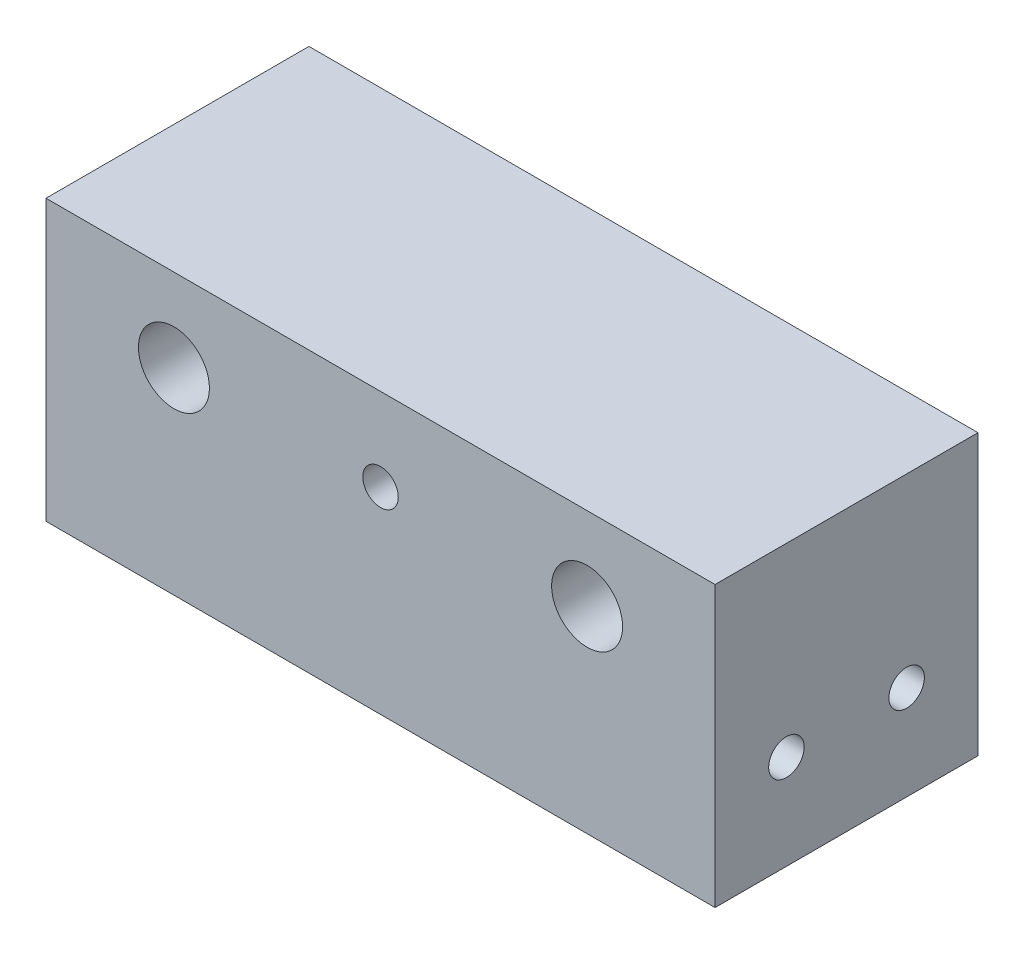
SolidWorks part; units mm, degrees
material "ABS"
ref_plane "X-Y Datum" through (0, 0, 0) normal (0, 0, 1) x (1, 0, 0)
ref_plane "X-Z Datum" through (0, 0, 0) normal (0, 1, 0) x (1, 0, 0)
ref_plane "Y-Z Datum" through (0, 0, 0) normal (1, 0, 0) x (0, 0, -1)
sketch "Sketch1" plane through (0, 0, 0) normal (0, 0, 1) x (1, 0, 0)
  line L1 (-28.275, 11.1125) -> (28.275, 11.1125)
  line L2 (-28.275, 11.1125) -> (-28.275, -11.1125)
  line L3 (-28.275, -11.1125) -> (28.275, -11.1125)
  line L4 (28.275, 11.1125) -> (28.275, -11.1125)
  line L5 (-28.275, 11.1125) -> (28.275, -11.1125) construction
  line L6 (-28.275, -11.1125) -> (28.275, 11.1125) construction
  point P0 (0, 0)
  dimension "D1" = 56.55
  dimension "D2" = 22.225
extrude "Boss-Extrude1" add sketch "Sketch1" along normal blind 22.225 contours L2 L3 L4 L1
sketch "Sketch2" plane through (0, 0, 22.225) normal (0, 0, 1) x (1, 0, 0)
  line L0 (-23.5453, 4.1125) -> (31.0951, 4.1125) construction
  line L1 (0, 11.1125) -> (0, -11.1125) construction
  line L2 (-28.275, 11.1125) -> (28.275, 11.1125) construction
  line L3 (-17.4625, 4.1125) -> (17.4625, 4.1125) construction
  line L4 (-28.275, -11.1125) -> (28.275, -11.1125) construction
  circle A0 centre (17.4625, 4.1125) radius 3
  circle A1 centre (-17.4625, 4.1125) radius 3
  circle A2 centre (0, 4.1125) radius 1.5
  point P10 (0, 4.1125)
  dimension "D1" = 6
  dimension "D4" = 3
  dimension "D2" = 34.925
  dimension "D3" = 7
extrude "Cut-Extrude1" cut sketch "Sketch2" against normal blind 10 contours A1 L0 L3 | L0 A1 L3 | L0 L3 A0 | L3 L0 A0 | A2 region at (17.4625, 4.1125, 22.225) region at (-17.4625, 4.1125, 22.225) region at (0, 4.1125, 22.225)
sketch "Sketch3" plane through (-28.275, 0, 0) normal (-1, 0, 0) x (0, 0, 1)
  line L0 (0, -4.5375) -> (22.225, -4.5375) construction
  line L1 (0, 11.1125) -> (0, -11.1125) construction
  line L2 (22.225, 184.8875) -> (22.225, -15.7125) construction
  line L3 (16.1925, -4.5375) -> (6.0325, -4.5375) construction
  line L4 (11.1125, 11.1125) -> (11.1125, -11.1125) construction
  line L5 (22.225, 11.1125) -> (0, 11.1125) construction
  line L6 (22.225, -11.1125) -> (0, -11.1125) construction
  line L7 (-277.475, -12.5375) -> (22.225, -12.5375) construction
  circle A0 centre (16.1925, -4.5375) radius 1.5
  circle A1 centre (6.0325, -4.5375) radius 1.5
  point P10 (11.1125, -4.5375)
  dimension "D1" = 3
  dimension "D2" = 10.16
  dimension "D3" = 8
extrude "Cut-Extrude2" cut sketch "Sketch3" against normal blind 10
sketch "Sketch5" plane through (0, -11.1125, 0) normal (0, -1, 0) x (1, 0, 0)
  line L4 (-28.275, 0) -> (28.275, 0)
  line L5 (28.275, 0) -> (28.275, 22.225)
  line L6 (28.275, 22.225) -> (-28.275, 22.225)
  line L7 (-28.275, 22.225) -> (-28.275, 0)
  line L8 (-28.275, 0) -> (28.275, 0)
  line L9 (28.275, 0) -> (28.275, 22.225)
  line L10 (28.275, 22.225) -> (-28.275, 22.225)
  line L11 (-28.275, 22.225) -> (-28.275, 0)
  dimension "D1" = 0
extrude "Boss-Extrude2" add sketch "Sketch5" along normal blind 1.4249
sketch "Sketch6" plane through (0, 0, 0) normal (0, 0, -1) x (-1, 0, 0)
  circle A0 centre (0, 0) radius 3.025
  dimension "D1" = 6.05
extrude "Cut-Extrude3" cut sketch "Sketch6" against normal blind 10
mirror "Mirror2" about plane through (0, 0, 0) normal (1, 0, 0) of "Cut-Extrude2"
